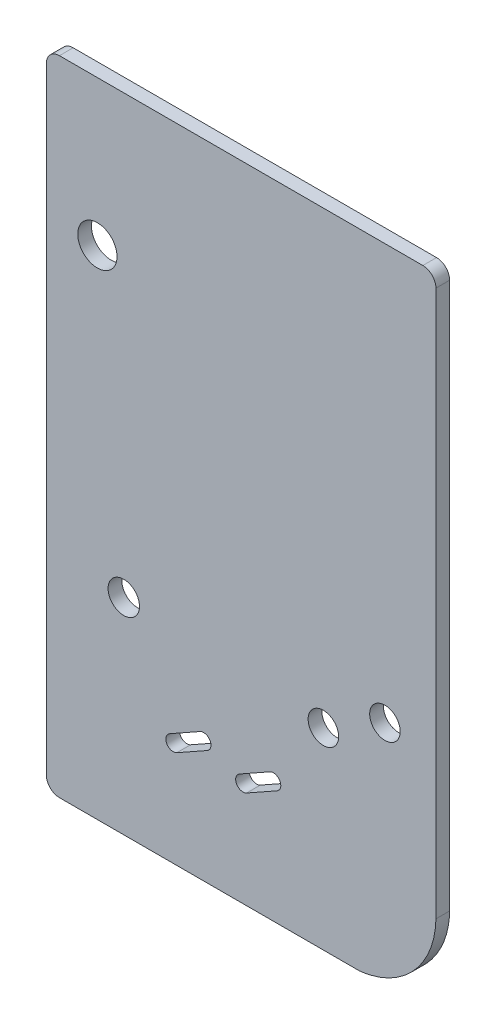
SolidWorks part; units mm, degrees
ref_plane "Front Plane" through (0, 0, 0) normal (0, 0, 1) x (1, 0, 0)
ref_plane "Top Plane" through (0, 0, 0) normal (0, 1, 0) x (1, 0, 0)
ref_plane "Right Plane" through (0, 0, 0) normal (1, 0, 0) x (0, 0, -1)
sketch "Sketch1" plane through (0, 0, 0) normal (0, 0, 1) x (1, 0, 0)
  line L1 (-26.2308, 73.6471) -> (38.6518, 73.6471)
  line L3 (-44.6471, -70.649) -> (-44.6471, 70.649)
  line L5 (27.0934, -73.6471) -> (-41.649, -73.6471)
  line L7 (-24.0867, 73.6955) -> (-35.6911, 73.6955)
  line L15 (-16.3293, -29.1587) -> (-16.3293, -23.8757)
  line L19 (44.6471, 67.6705) -> (44.6471, -53.896)
  line L20 (-0.4012, -48.3225) -> (6.5714, -44.4005)
  line L21 (8.2266, -47.343) -> (1.254, -51.2651)
  line L22 (-44.6471, 73.6471) -> (44.6471, 73.6471)
  line L23 (44.6471, 73.6471) -> (44.6471, -73.6471)
  line L24 (44.6471, -73.6471) -> (-44.6471, -73.6471)
  line L25 (-44.6471, -73.6471) -> (-44.6471, 73.6471)
  line L26 (-25.1679, 56.2163) -> (-25.1679, 10.288)
  line L27 (-25.1679, 10.288) -> (24.9222, 10.288)
  line L28 (24.9222, 10.288) -> (24.9222, 56.2163)
  line L29 (24.9222, 56.2163) -> (-25.1679, 56.2163)
  line L34 (36.6393, 62.5051) -> (-36.0272, 62.5051)
  line L35 (-38.5272, 60.0051) -> (-38.5272, 6.9331)
  line L36 (-36.0272, 4.4331) -> (29.8893, 4.4331)
  line L37 (39.1393, 13.6831) -> (39.1393, 60.0051)
  line L38 (-16.4012, -48.3225) -> (-9.4286, -44.4005)
  line L39 (-7.7734, -47.343) -> (-14.746, -51.2651)
  line L41 (44.6471, 70.649) -> (44.6471, 67.6705)
  line L43 (38.6518, 73.6471) -> (41.649, 73.6471)
  line L45 (-41.649, 73.6471) -> (-26.2308, 73.6471)
  line L150 (42.2525, -55.0539) -> (42.2511, -54.9499)
  circle A0 centre (34.1495, 24.0914) radius 10.7
  circle A2 centre (-26.9008, -26.5172) radius 3.6
  arc A3 (8.2266, -47.343) -> (6.5714, -44.4005) centre (7.399, -45.8717) ccw
  arc A6 (-16.4012, -48.3225) -> (-14.746, -51.2651) centre (-15.5736, -49.7938) ccw
  arc A7 (-7.7734, -47.343) -> (-9.4286, -44.4005) centre (-8.601, -45.8717) ccw
  circle A15 centre (18.8495, -29.5462) radius 3.5
  circle A16 centre (32.9602, -21.4767) radius 3.5
  arc A17 (-0.4012, -48.3225) -> (1.254, -51.2651) centre (0.4264, -49.7938) ccw
  circle A19 centre (-32.9539, 40.3411) radius 4.5
  arc A24 (39.1393, 60.0051) -> (36.6393, 62.5051) centre (36.6393, 60.0051) ccw
  arc A25 (-36.0272, 62.5051) -> (-38.5272, 60.0051) centre (-36.0272, 60.0051) ccw
  arc A26 (-38.5272, 6.9331) -> (-36.0272, 4.4331) centre (-36.0272, 6.9331) ccw
  arc A27 (29.8893, 4.4331) -> (39.1393, 13.6831) centre (29.8893, 13.6831) ccw
  ellipse E3 centre (-41.649, -70.649) end of major axis (-39.5276, -72.7703) minor radius 2.9963 (-44.6471, -70.649) -> (-41.649, -73.6471) ccw
  ellipse E5 centre (41.649, 70.649) end of major axis (39.5276, 72.7703) minor radius 2.9963 (44.6471, 70.649) -> (41.649, 73.6471) ccw
  ellipse E7 centre (-41.649, 70.649) end of major axis (-43.7703, 68.5276) minor radius 2.9963 (-41.649, 73.6471) -> (-44.6471, 70.649) ccw
  spline S1 degree 3 poles (44.6485, -54) (44.663, -55.258) (44.5568, -56.5068) (44.2157, -58.3662) (44.0715, -58.9837) (43.7192, -60.2138) (43.5128, -60.8202) (42.8075, -62.6008) (42.2221, -63.7422) (41.3373, -65.1085) (41.1525, -65.3788) (40.7717, -65.907) (40.5751, -66.1657) (39.9672, -66.9256) (39.1083, -67.8961) (38.1523, -68.7812) (37.1464, -69.6222) (36.6152, -70.0225) (34.9811, -71.1285) (33.8311, -71.748) (32.3187, -72.3766) (32.0124, -72.495) (31.3922, -72.7168) (31.0776, -72.8204) (30.1333, -73.105) (29.5001, -73.2613) (27.5898, -73.6337) (26.302, -73.7542) (25, -73.7456) knots 0 0 0 0 0.125 0.125 0.1875 0.1875 0.25 0.25 0.375 0.375 0.40625 0.40625 0.4375 0.4375 0.5 0.5625 0.5625 0.625 0.625 0.75 0.75 0.78125 0.78125 0.8125 0.8125 0.875 0.875 1 1 1 1
  dimension "D4" = 21.4
  dimension "D8" = 7
  dimension "D11" = 9
  dimension "D12" = 7.2
  dimension "D1" = 10.4977
  dimension "D2" = 89.2943
  dimension "D3" = 147.2943
  dimension "D5" = 25.9097
  dimension "D6" = 8.0696
  dimension "D7" = 14.1107
  dimension "D9" = 7.7861
  dimension "D10" = 22.1641
  dimension "D13" = 10.5715
extrude "Boss-Extrude1" add sketch "Sketch1" along normal blind 3.14 contours S1 L23 L19 A0 L37 A27 L36 A26 L35 A25 L34 A24 E5 L22 L1 E7 L3 E3 L5 A17 L20 A3 L21 A16 A15 A7 L39 A6 L38 A2 | L23 A0 L37 region at (-0.9227, -16.9165, 0) region at (41.4616, 24.0914, 0)
extrude "Boss-Extrude2" add sketch "Sketch1<3>" along normal blind 3.14 contours L36 A27 L37 A0 L28 L27 L26 L29 A24 L34 A25 L35 A26 A19 | L37 A0 L28 region at (30.9538, 35.3151, 0) region at (32.4596, 24.0914, 0)
sketch "Sketch1<3>" plane through (0, 0, 0) normal (0, 0, 1) x (1, 0, 0) same geometry as "Sketch1"
extrude "Boss-Extrude3" add sketch "Sketch1<4>" along normal blind 3.14 contours A0 L28 L29 L26 L27 | L28 A0 region at (-0.2381, 33.2953, 0) region at (24.3295, 24.0914, 0)
sketch "Sketch1<4>" plane through (0, 0, 0) normal (0, 0, 1) x (1, 0, 0) same geometry as "Sketch1"
